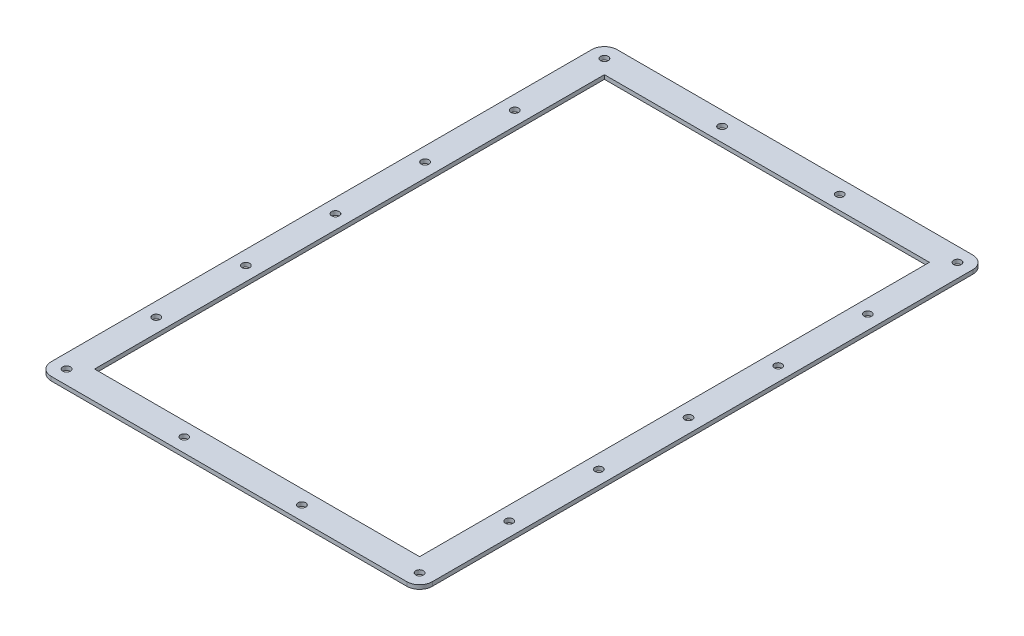
SolidWorks part; units mm, degrees
material "5052-H32"
ref_plane "Front Plane" through (0, 0, 0) normal (0, 0, 1) x (1, 0, 0)
ref_plane "Top Plane" through (0, 0, 0) normal (0, 1, 0) x (1, 0, 0)
ref_plane "Right Plane" through (0, 0, 0) normal (1, 0, 0) x (0, 0, -1)
sketch "Sketch1" plane through (0, 0, 0) normal (0, 1, 0) x (1, 0, 0)
  line L0 (-147, 172) -> (152, 172)
  line L1 (-125, -250) -> (130, -250)
  line L2 (-125, -250) -> (-125, 150)
  line L3 (-125, 150) -> (130, 150)
  line L4 (130, -250) -> (130, 150)
  line L5 (-125, -250) -> (130, 150) construction
  line L6 (-125, 150) -> (130, -250) construction
  line L7 (152, -272) -> (152, 172)
  line L8 (-147, -272) -> (152, -272)
  line L9 (-147, -272) -> (-147, 172)
  line L12 (130, -50) -> (-125, -50) construction
  circle A34 centre (141, 161) radius 3
  circle A35 centre (48.6667, 161) radius 3
  circle A36 centre (-43.6667, 161) radius 3
  circle A37 centre (-136, 161) radius 3
  circle A90 centre (141, 90.6667) radius 3
  circle A91 centre (141, 20.3333) radius 3
  circle A92 centre (141, -50) radius 3
  circle A93 centre (141, -120.3333) radius 3
  circle A94 centre (141, -190.6667) radius 3
  circle A102 centre (-136, 90.6667) radius 3
  circle A103 centre (141, -261) radius 3
  circle A106 centre (-136, 20.3333) radius 3
  circle A107 centre (48.6667, -261) radius 3
  circle A110 centre (-136, -50) radius 3
  circle A111 centre (-43.6667, -261) radius 3
  circle A114 centre (-136, -120.3333) radius 3
  circle A115 centre (-136, -261) radius 3
  circle A118 centre (-136, -190.6667) radius 3
  circle A119 centre (48.6667, -120.3333) radius 3 [skipped]
  circle A120 centre (-43.6667, -120.3333) radius 3 [skipped]
  circle A121 centre (48.6667, 90.6667) radius 3 [skipped]
  circle A122 centre (-43.6667, 90.6667) radius 3 [skipped]
  circle A123 centre (48.6667, 20.3333) radius 3 [skipped]
  circle A124 centre (48.6667, -50) radius 3 [skipped]
  circle A125 centre (-43.6667, -50) radius 3 [skipped]
  circle A126 centre (-43.6667, 20.3333) radius 3 [skipped]
  circle A127 centre (48.6667, -190.6667) radius 3 [skipped]
  circle A128 centre (-43.6667, -190.6667) radius 3 [skipped]
  dimension "D4" = 6
  dimension "D2" = 400
  dimension "D1" = 22
  dimension "D3" = 255
  dimension "D5" = 11
  dimension "D6" = 11
  dimension "D9" = 70.3333
  dimension "D10" = 92.3333
  dimension "D7" = 4
  dimension "D8" = 7
extrude "Boss-Extrude1" add sketch "Sketch1" along normal blind 3.175 contours L9 L8 L7 L0 L4 L1 L2 L3 A34 region at (2.5, 0, -166.6471)
fillet "Fillet1" radius 10 4 edges at (152, 1.5875, 272) (-147, 1.5875, 272) (152, 1.5875, -172) (-147, 1.5875, -172)
equation "\"L\"= 400"
equation "\"W\"= 255"
equation "\"H\"= 110"
equation "\"Compartment Width\"= 80"
equation "\"T\"= 4.7625 * 2 / 3"
equation "\"Inside Fillet Radius\"= 5.55625"
equation "\"Hole\"=15"
equation "\"D2@Sketch1\"=\"L\""
equation "\"D1@Boss-Extrude1\"=\"T\""
equation "\"D3@Sketch1\"=\"W\""
equation "\"D9@Sketch1\"=(\"L\"+22)/6"
equation "\"D10@Sketch1\"=(\"W\"+22)/3"
equation "\"Offset\"= 30"
equation "\"Wheel to Wall\"= 43"
